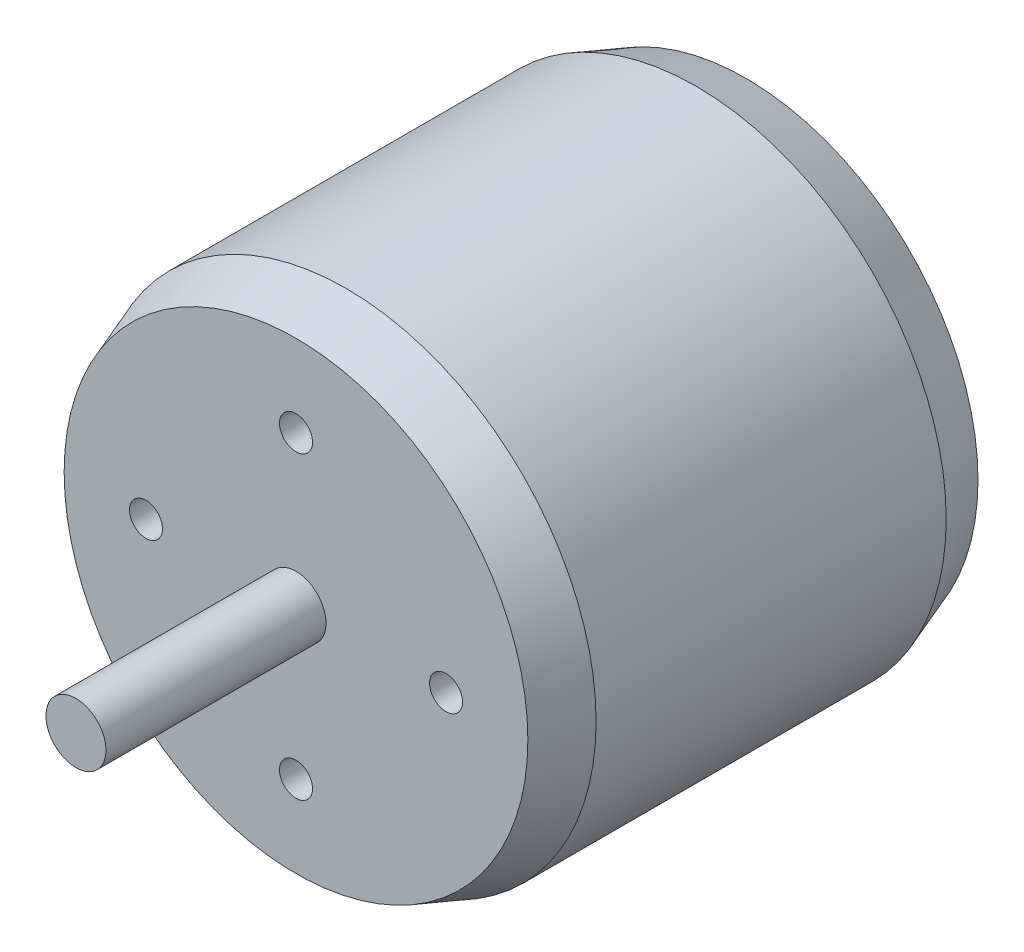
SolidWorks part; units mm, degrees
ref_plane "Front Plane" through (0, 0, 0) normal (0, 0, 1) x (1, 0, 0)
ref_plane "Top Plane" through (0, 0, 0) normal (0, 1, 0) x (1, 0, 0)
ref_plane "Right Plane" through (0, 0, 0) normal (1, 0, 0) x (0, 0, -1)
sketch "Sketch1" plane through (0, 0, 0) normal (0, 0, 1) x (1, 0, 0)
  circle A0 centre (0, 0) radius 25
  dimension "D1" = 50
extrude "Boss-Extrude1" add sketch "Sketch1" along normal blind 45
chamfer "Chamfer1" distance 5 angle 20 2 edges at (25, 0, 0) (25, 0, 45) first distance on face at (25, 0, 45)
sketch "Sketch2" plane through (0, 0, 45) normal (0, 0, 1) x (1, 0, 0)
  circle A0 centre (0, 0) radius 3
  dimension "D1" = 6
extrude "Boss-Extrude2" add sketch "Sketch2" along normal offset from surface (22 mm away) 67 up to face at (23.1801, 0, 0)
sketch "Sketch3" plane through (0, 0, 0) normal (0, 0, -1) x (-1, 0, 0)
  circle A0 centre (0, 0) radius 3
  dimension "D1" = 6
extrude "Boss-Extrude3" add sketch "Sketch3" along normal blind 2
sketch "Sketch4" plane through (0, 0, 0) normal (0, 0, -1) x (-1, 0, 0)
  circle A0 centre (0, 0) radius 10 construction
  point P3 (0, 10)
  dimension "D1" = 20
hole_wizard "Tap Drill for M3x0.5 Tap1" positions "Sketch4" profile "Sketch5" hole size "M3x0.5" standard "ANSI Metric"
sketch "Sketch5" plane through (0, 10, 0) normal (1, 0, 0) x (0, 1, 0)
  line L0 (0, 0) -> (0, 10.7511)
  line L1 (0, 10.7511) -> (1.25, 10)
  line L2 (1.25, 10) -> (1.25, 0)
  line L5 (1.25, 0) -> (0, 0)
  line L10 (0, 10.7511) -> (-1.25, 10) construction
  line L11 (0, -6.35) -> (0, 107.95) construction
  dimension "Hole Dia." = 2.5
  dimension "Hole Depth" = 10
  dimension "Drill Angle" = 118
pattern_circular "CirPattern1" count 4 over 360 about axis through (0, 0, 45) along (0, 0, -1) of "Tap Drill for M3x0.5 Tap1" reverse direction yes
sketch "Sketch6" plane through (0, 0, 45) normal (0, 0, 1) x (1, 0, 0)
  line L0 (0, 0) -> (15, 0) construction
  circle A0 centre (0, 0) radius 15 construction
  dimension "D1" = 30
hole_wizard "Tap Drill for M4x0.7 Tap1" positions "Sketch7" profile "Sketch8" hole size "M4x0.7" standard "ANSI Metric"
sketch "Sketch7" plane through (0, 0, 45) normal (0, 0, 1) x (1, 0, 0)
  point P0 (15, 0)
sketch "Sketch8" plane through (15, 0, 45) normal (1, 0, 0) x (0, -1, 0)
  line L0 (0, 0) -> (0, 10.9914)
  line L1 (0, 10.9914) -> (1.65, 10)
  line L2 (1.65, 10) -> (1.65, 0)
  line L5 (1.65, 0) -> (0, 0)
  line L10 (0, 10.9914) -> (-1.65, 10) construction
  line L11 (0, -6.35) -> (0, 107.95) construction
  dimension "Hole Dia." = 3.3
  dimension "Hole Depth" = 10
  dimension "Drill Angle" = 118
pattern_circular "CirPattern2" count 4 over 360 about axis through (0, 0, 45) along (0, 0, -1) of "Tap Drill for M4x0.7 Tap1"
